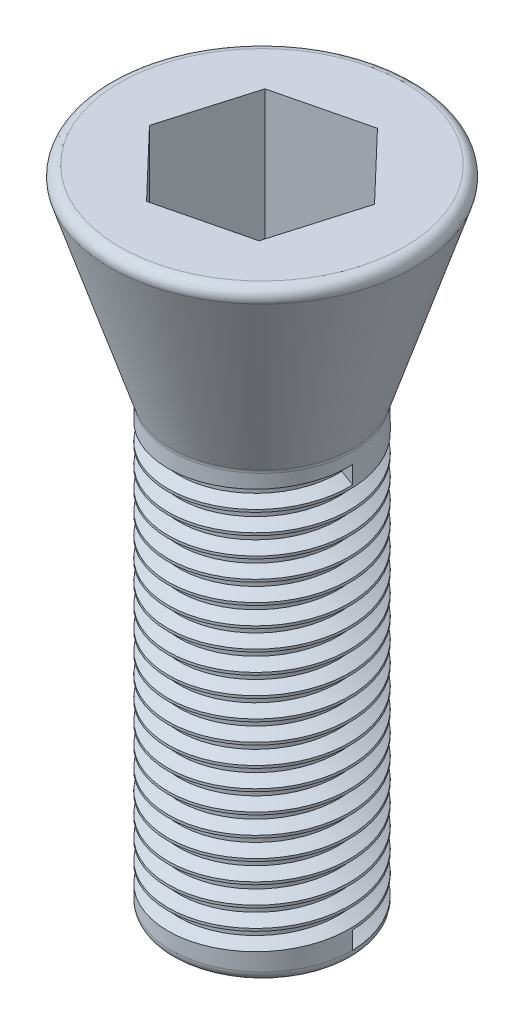
SolidWorks part; units mm, degrees
material "ASTM A36 Steel"
ref_plane "Front Plane" through (0, 0, 0) normal (0, 0, 1) x (1, 0, 0)
ref_plane "Top Plane" through (0, 0, 0) normal (0, 1, 0) x (1, 0, 0)
ref_plane "Right Plane" through (0, 0, 0) normal (1, 0, 0) x (0, 0, -1)
sketch "Sketch1" plane through (0, 0, 0) normal (0, 0, 1) x (1, 0, 0)
  line L0 (0, 0) -> (7.75, 0)
  line L1 (0, 0) -> (0, -10)
  line L3 (7.75, 0) -> (4.5, -10)
  line L4 (4.5, -10) -> (4.5, -32)
  line L5 (4.5, -32) -> (0, -32)
  line L6 (0, -32) -> (0, -10)
revolve "Revolve1" add sketch "Sketch1" angle 360 about L1
sketch "Sketch2" plane through (0, 0, 0) normal (0, 1, 0) x (1, 0, 0)
  line L1 (1.2942, 4.4338) -> (-3.1927, 3.3377)
  line L2 (-3.1927, 3.3377) -> (-4.4869, -1.0961)
  line L3 (-4.4869, -1.0961) -> (-1.2942, -4.4338)
  line L4 (-1.2942, -4.4338) -> (3.1927, -3.3377)
  line L5 (3.1927, -3.3377) -> (4.4869, 1.0961)
  line L6 (4.4869, 1.0961) -> (1.2942, 4.4338)
  circle A0 centre (0, 0) radius 4 construction
extrude "Cut-Extrude1" cut sketch "Sketch2" against normal blind 7
fillet "Fillet1" radius 0.5 3 edges at (-4.5, -32, 0) (-4.5, -10, 0) (-7.75, 0, 0)
thread "Thread1" pitch 1 method cut profile "Thread Profile1" start angle 0, offset 0, length 20, pitch 1, diameter 9
ref_plane "Plane1" through (4.5, -31.5, 0) normal (0, 0, 1) x (1, 0, 0)
sketch "Thread Profile1" plane through (4.5, -31.5, 0) normal (0, 0, 1) x (1, 0, 0)
  line L0 (0, 0) -> (0, 1) construction
  line L11 (0, 0) -> (0, 0.875)
  line L12 (0, 0.875) -> (-0.5413, 0.5625)
  line L13 (-0.5413, 0.5625) -> (-0.5413, 0.3125)
  line L15 (-0.5413, 0.3125) -> (0, 0)
  line L17 (-0.5413, 0.4375) -> (0, 0.4375) construction
  point P2 (0, 0)
  dimension "Pitch" = 1
  dimension "Profile_Angle" = 60
  dimension "Profile_Land" = 0.25
  dimension "Profile_Height" = 0.5413
